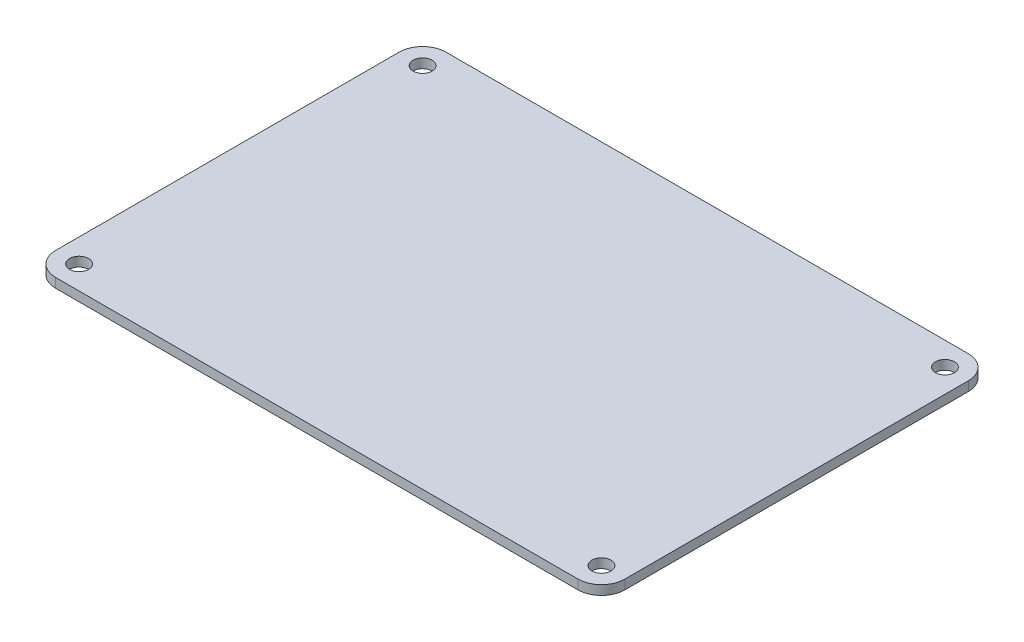
SolidWorks part; units mm, degrees
note: The reader was unsure of these and kept them because the rebuilt part matched: shared geometry of "Sketch1<5>", "Sketch1<6>".
ref_plane "Front Plane" through (0, 0, 0) normal (0, 0, 1) x (1, 0, 0)
ref_plane "Top Plane" through (0, 0, 0) normal (0, 1, 0) x (1, 0, 0)
ref_plane "Right Plane" through (0, 0, 0) normal (1, 0, 0) x (0, 0, -1)
sketch "Sketch1" plane through (0, 0, 0) normal (0, 1, 0) x (1, 0, 0)
  line L0 (55.75, 36.66) -> (58.25, 36.66)
  line L1 (0, 0) -> (55.75, 0)
  line L2 (0, 0) -> (0, 36.66)
  line L3 (0, 36.66) -> (55.75, 36.66)
  line L4 (55.75, 0) -> (55.75, 36.66)
  line L5 (55.75, 36.66) -> (55.75, 39.16)
  line L6 (55.75, 0) -> (58.25, 0)
  line L7 (55.75, 0) -> (55.75, -2.5)
  line L8 (0, 0) -> (0, -2.5)
  line L9 (0, 0) -> (-2.5, 0)
  line L10 (0, 36.66) -> (-2.5, 36.66)
  line L11 (0, 36.66) -> (0, 39.16)
  line L12 (-2.5, 36.66) -> (-2.5, 0)
  line L13 (0, -2.5) -> (55.75, -2.5)
  line L14 (58.25, 0) -> (58.25, 36.66)
  line L15 (55.75, 39.16) -> (0, 39.16)
  circle A0 centre (55.75, 0) radius 1.012
  circle A1 centre (0, 0) radius 1.012
  circle A2 centre (0, 36.66) radius 1.012
  circle A3 centre (55.75, 36.66) radius 1.012
  circle A4 centre (55.75, 0) radius 2.5
  circle A5 centre (0, 0) radius 2.5
  circle A6 centre (0, 36.66) radius 2.5
  circle A7 centre (55.75, 36.66) radius 2.5
  dimension "D3" = 2.024
  dimension "D4" = 2.024
  dimension "D5" = 2.024
  dimension "D6" = 2.024
  dimension "D1" = 55.75
  dimension "D2" = 36.66
extrude "Boss-Extrude3" add sketch "Sketch1" along normal blind 2 contours A7 L3 A6 L2 A5 L1 A4 L4 | A5 L13 A4 L1 | A7 L4 A4 L14 | A7 L15 A6 L3 | A6 L12 A5 L2
extrude "Boss-Extrude4" add sketch "Sketch1<5>" along normal blind 2 contours L7 A4 L6 A0 | L4 A4 L1 A0 | L1 A4 L7 A0 | L6 A4 L4 A0
sketch "Sketch1<5>" plane through (0, 0, 0) normal (0, 1, 0) x (1, 0, 0) same geometry as "Sketch1"
extrude "Boss-Extrude5" add sketch "Sketch1<6>" along normal blind 2 contours L9 A5 L8 A1 | L2 A5 L9 A1 | L1 A5 L2 A1 | L8 A5 L1 A1 | L10 A6 L2 A2 | L11 A6 L10 A2 | L3 A6 L11 A2 | L2 A6 L3 A2 | L3 A7 L4 A3 | L5 A7 L3 A3 | L0 A7 L5 A3 | L4 A7 L0 A3
sketch "Sketch1<6>" plane through (0, 0, 0) normal (0, 1, 0) x (1, 0, 0) same geometry as "Sketch1"
sketch "Sketch2" plane through (0, 2, 0) normal (0, 1, 0) x (1, 0, 0)
  line L2 (27.875, 29.16) -> (33.225, 29.16)
  line L3 (27.875, 29.16) -> (22.525, 29.16)
  line L4 (22.525, 29.16) -> (22.525, 30.9766)
  line L5 (22.525, 29.16) -> (22.525, 27.3434)
  line L6 (33.225, 29.16) -> (33.225, 30.9766)
  line L7 (33.225, 29.16) -> (33.225, 27.3434)
  line L8 (22.525, 30.9766) -> (33.225, 30.9766)
  line L9 (22.525, 27.3434) -> (33.225, 27.3434)
  line L10 (33.225, 29.16) -> (33.225, 30.16)
  line L11 (33.225, 29.16) -> (33.225, 28.16)
  line L12 (27.875, 29.16) -> (33.925, 29.16)
  line L13 (27.875, 29.16) -> (21.825, 29.16)
  line L14 (21.825, 29.16) -> (21.825, 30.9766)
  line L15 (21.825, 30.9766) -> (22.525, 30.9766)
  line L16 (21.825, 29.16) -> (21.825, 27.3434)
  line L17 (21.825, 27.3434) -> (22.525, 27.3434)
  line L18 (33.925, 29.16) -> (33.925, 30.9766)
  line L19 (33.925, 30.9766) -> (33.225, 30.9766)
  line L20 (33.225, 27.3434) -> (33.925, 27.3434)
  line L21 (33.925, 27.3434) -> (33.925, 29.16)
  line L22 (33.225, 30.16) -> (33.925, 30.16)
  line L23 (33.225, 28.16) -> (33.925, 28.16)
  line L24 (22.525, 29.16) -> (22.525, 30.16)
  line L25 (22.525, 29.16) -> (22.525, 28.16)
  line L26 (22.525, 28.16) -> (21.825, 28.16)
  line L27 (22.525, 30.16) -> (21.825, 30.16)
  line L28 (27.875, 39.16) -> (27.875, -2.5)
  line L29 (55.75, 39.16) -> (0, 39.16) construction
  line L30 (0, -2.5) -> (55.75, -2.5) construction
  circle A1 centre (55.75, 0) radius 2.5 construction
  circle A2 centre (0, 0) radius 2.5 construction
  circle A4 centre (27.875, 29.16) radius 5.65
  dimension "D1" = 11.3
  dimension "D2" = 5.35
  dimension "D3" = 5.35
  dimension "D4" = 1
  dimension "D5" = 1
  dimension "D6" = 6.05
  dimension "D7" = 6.05
  dimension "D8" = 1
  dimension "D9" = 1
  dimension "D10" = 10
extrude "Cut-Extrude21" cut sketch "Sketch2" against normal blind 10
sketch "Sketch7" plane through (0, 2, 0) normal (0, 1, 0) x (1, 0, 0)
  line L1 (55.75, -2.5) -> (58.25, -2.5)
  line L2 (55.75, -2.5) -> (55.75, 0)
  line L3 (55.75, 0) -> (58.25, 0)
  line L4 (58.25, -2.5) -> (58.25, 0)
  line L5 (-2.5, 36.66) -> (0, 36.66)
  line L6 (-2.5, 36.66) -> (-2.5, 39.16)
  line L7 (-2.5, 39.16) -> (0, 39.16)
  line L8 (0, 36.66) -> (0, 39.16)
  line L9 (-2.5, 39.16) -> (58.25, 39.16)
  line L10 (-2.5, 39.16) -> (-2.5, -2.5)
  line L11 (-2.5, -2.5) -> (58.25, -2.5)
  line L12 (58.25, 39.16) -> (58.25, -2.5)
  arc A0 (55.75, -2.5) -> (58.25, 0) centre (55.75, 0) ccw construction
extrude "Cut-Extrude23" cut sketch "Sketch7" against normal blind 1
sketch "Sketch8" plane through (0, 1, 0) normal (0, 1, 0) x (1, 0, 0)
  line L1 (17.4142, 36.181) -> (39.5166, 36.181)
  line L2 (17.4142, 36.181) -> (17.4142, 21.2469)
  line L3 (17.4142, 21.2469) -> (39.5166, 21.2469)
  line L4 (39.5166, 36.181) -> (39.5166, 21.2469)
extrude "Boss-Extrude6" add sketch "Sketch8" against normal blind 1
